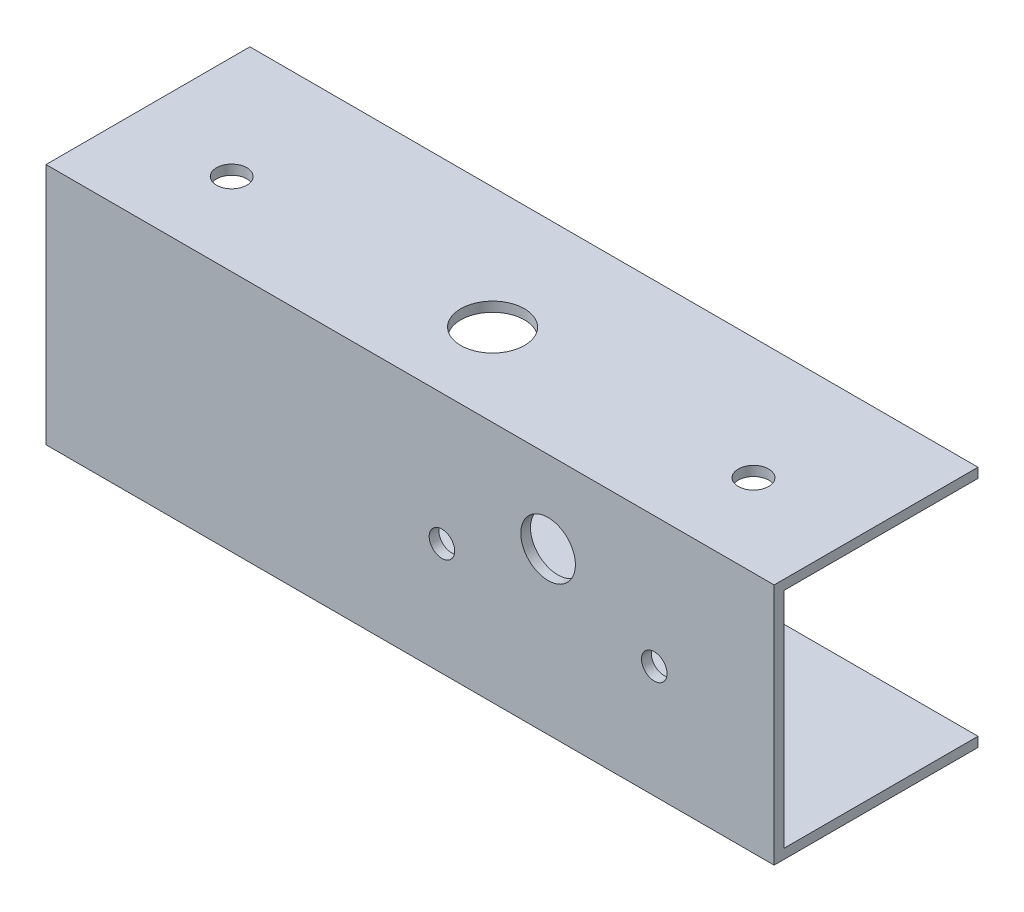
SolidWorks part; units mm, degrees
ref_plane "Front Plane" through (0, 0, 0) normal (0, 0, 1) x (1, 0, 0)
ref_plane "Top Plane" through (0, 0, 0) normal (0, 1, 0) x (1, 0, 0)
ref_plane "Right Plane" through (0, 0, 0) normal (1, 0, 0) x (0, 0, -1)
sketch "Sketch1" plane through (0, 0, 0) normal (0, 1, 0) x (1, 0, 0)
  line L0 (0, -16.0011) -> (0, 16.0011) construction
  line L14 (-60, -12) -> (60, -12)
  line L15 (-60, -12) -> (-60, 20)
  line L16 (-60, 20) -> (60, 20)
  line L17 (60, -12) -> (60, 20)
  circle A0 centre (0, 0) radius 5.25
  circle A1 centre (-43, 0) radius 2.5
  circle A2 centre (43, 0) radius 2.5
  point P0 (0, 0)
  dimension "D3" = 10.5
  dimension "D4" = 43
  dimension "D5" = 5
  dimension "D8" = 12
  dimension "D1" = 20
  dimension "D2" = 12
  dimension "D6" = 120
  dimension "D7" = 60
other "AlignGroup1"
other "AlignGroup2"
extrude "Boss-Extrude1" add sketch "Sketch1" along normal blind 1.6
sketch "Sketch3" plane through (0, 0, 0) normal (0, -1, 0) x (1, 0, 0)
  line L1 (-60, 12) -> (60, 12)
  line L2 (-60, 12) -> (-60, 13.6)
  line L3 (-60, 13.6) -> (60, 13.6)
  line L4 (60, 12) -> (60, 13.6)
  dimension "D1" = 1.6
extrude "Boss-Extrude3" add sketch "Sketch3" against normal blind 40
ref_plane "Plane1" through (0, 20, 0) normal (0, 1, 0) x (1, 0, 0)
mirror "Mirror1" about plane through (0, 20, 0) normal (0, 1, 0) of "Boss-Extrude1"
sketch "Sketch4" plane through (0, 0, 13.6) normal (0, 0, 1) x (1, 0, 0)
  line L0 (60, 0) -> (-60, 0) construction
  line L1 (60, 40) -> (-60, 40) construction
  line L2 (22.75, 26.5) -> (22.75, 5.2725)
  circle A0 centre (5.25, 18.5) radius 2.1
  circle A1 centre (22.75, 26.5) radius 4.5
  circle A2 centre (40.25, 18.5) radius 2.1
  point P6 (0, 40)
  dimension "D1" = 4.2
  dimension "D4" = 9
  dimension "D2" = 18.5
  dimension "D3" = 5.25
  dimension "D5" = 8
  dimension "D6" = 17.5
extrude "Cut-Extrude1" cut sketch "Sketch4" against normal blind 2 contours A0 | A1 | A2 region at (5.25, 18.5, 13.6) region at (25.842, 23.408, 13.6) region at (40.25, 18.5, 13.6)
